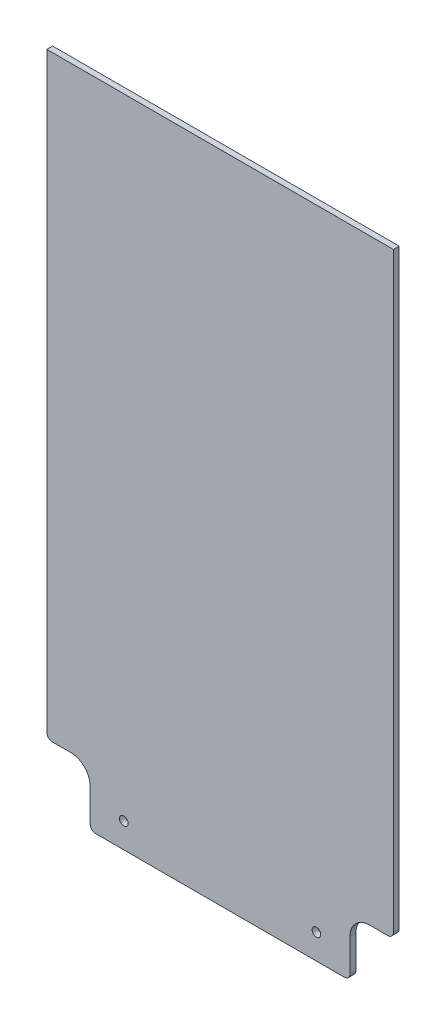
SolidWorks part; units mm, degrees
ref_plane "Plan de face" through (0, 0, 0) normal (0, 0, 1) x (1, 0, 0)
ref_plane "Plan de dessus" through (0, 0, 0) normal (0, 1, 0) x (1, 0, 0)
ref_plane "Plan de droite" through (0, 0, 0) normal (1, 0, 0) x (0, 0, -1)
sketch "Esquisse1" plane through (0, 0, 0) normal (0, 0, 1) x (1, 0, 0)
  line L1 (0, 0) -> (180, 0)
  line L2 (0, 0) -> (0, 340)
  line L3 (0, 340) -> (180, 340)
  line L4 (180, 0) -> (180, 340)
  dimension "D1" = 180
  dimension "D2" = 340
extrude "Boss.-Extru.1" add sketch "Esquisse1" along normal blind 3
sketch "Esquisse2" plane through (0, 0, 3) normal (0, 0, 1) x (1, 0, 0)
  line L0 (0, 13) -> (180, 13) construction
  line L1 (0, 340) -> (0, 0) construction
  line L2 (180, 0) -> (180, 340) construction
  line L3 (0, 0) -> (180, 0) construction
  circle A0 centre (40, 13) radius 2.25
  circle A1 centre (140, 13) radius 2.25
  dimension "D1" = 4.5
  dimension "D3" = 40
  dimension "D4" = 100
  dimension "D2" = 13
extrude "Enlèv. mat.-Extru.1" cut sketch "Esquisse2" against normal through all both and the other way through all
sketch "Esquisse3" plane through (0, 0, 3) normal (0, 0, 1) x (1, 0, 0)
  line L1 (0, 0) -> (22.5, 0)
  line L2 (0, 0) -> (0, 30)
  line L3 (0, 30) -> (22.5, 30)
  line L4 (22.5, 0) -> (22.5, 30)
  line L5 (180, 0) -> (157.5, 0)
  line L6 (180, 0) -> (180, 30)
  line L7 (180, 30) -> (157.5, 30)
  line L8 (157.5, 0) -> (157.5, 30)
  dimension "D1" = 30
  dimension "D2" = 22.5
  dimension "D3" = 22.5
extrude "Enlèv. mat.-Extru.2" cut sketch "Esquisse3" against normal through all both and the other way through all
fillet "Congé1" radius 10 2 edges at (157.5, 30, 1.5) (22.5, 30, 1.5)
fillet "Congé2" radius 3 4 edges at (0, 30, 1.5) (22.5, 0, 1.5) (180, 30, 1.5) (157.5, 0, 1.5)
